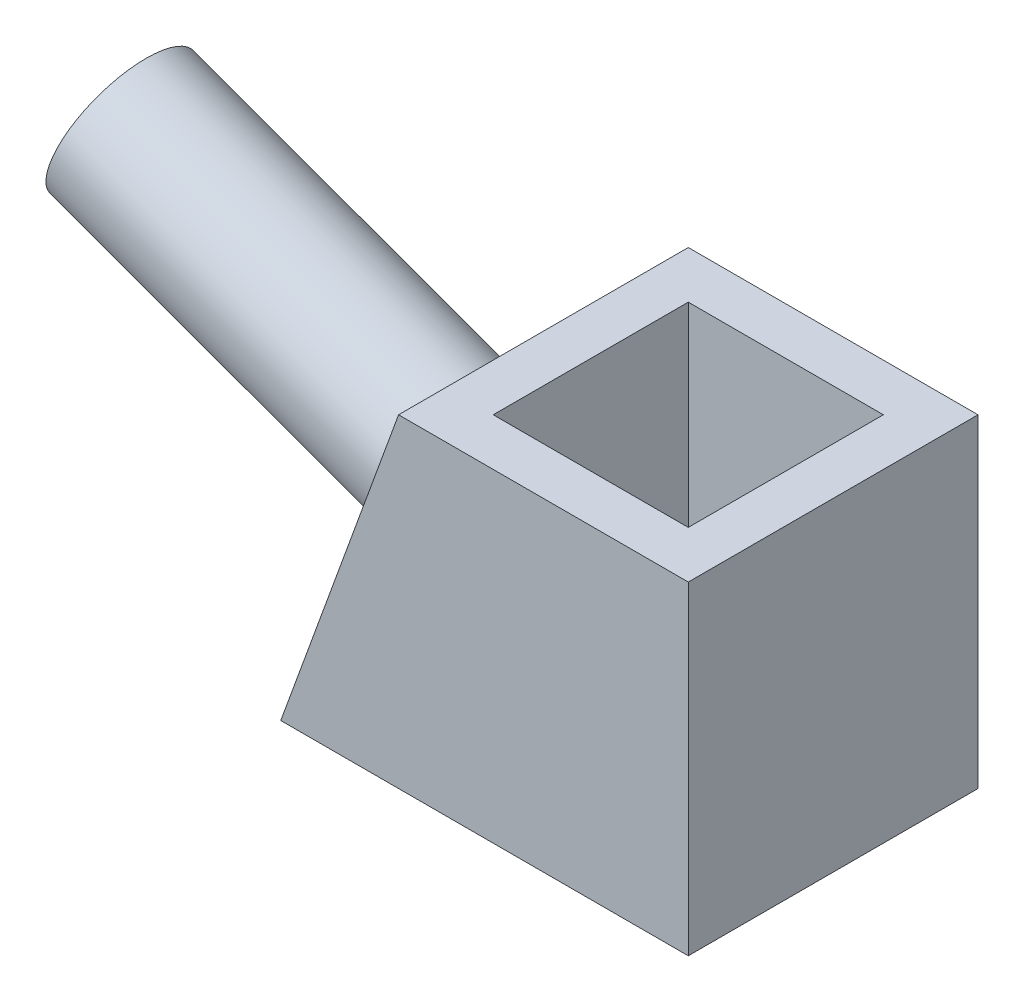
SolidWorks part; units mm, degrees
note: '?' marks a value the reader was unsure of.
ref_plane "Front Plane" through (0, 0, 0) normal (0, 0, 1) x (1, 0, 0)
ref_plane "Top Plane" through (0, 0, 0) normal (0, 1, 0) x (1, 0, 0)
ref_plane "Right Plane" through (0, 0, 0) normal (1, 0, 0) x (0, 0, -1)
sketch "Sketch1" plane through (0, 0, 0) normal (0, 1, 0) x (1, 0, 0)
  line L1 (0, 0) -> (53.594, 0)
  line L2 (0, 0) -> (0, 38.1)
  line L3 (0, 38.1) -> (53.594, 38.1)
  line L4 (53.594, 0) -> (53.594, 38.1)
  dimension "D1" = 53.594
  dimension "D2" = 38.1
extrude "Boss-Extrude1" add sketch "Sketch1" along normal blind 42.5694
sketch "Sketch4" plane through (0, 0, 0) normal (0, 0, 1) x (1, 0, 0)
  line L0 (53.594, 42.5694) -> (15.494, 42.5694)
  line L1 (0, 42.5694) -> (53.594, 42.5694) construction
  line L2 (15.494, 42.5694) -> (-0.4078, -1.1203)
  line L3 (0, 42.5694) -> (0, 0)
  line L4 (0, 42.5694) -> (0, 0) construction
  line L5 (15.494, 42.5694) -> (0, 42.5694)
  line M5 (53.594, 42.5694) -> (0, 42.5694)
  line M6 (0, 42.5694) -> (0, 0)
  dimension "D1" = 38.1
  dimension "D2" = 110
extrude "Cut-Extrude1" cut sketch "Sketch4" against normal through all contours L2 M5 M6
sketch "Sketch5" plane through (0, 42.5694, 0) normal (0, 1, 0) x (1, 0, 0)
  line L7 (15.494, 0) -> (53.594, 0) construction
  line L8 (53.594, 0) -> (53.594, 38.1) construction
  line L10 (47.371, 31.877) -> (21.717, 31.877)
  line L11 (47.371, 31.877) -> (47.371, 6.223)
  line L12 (47.371, 6.223) -> (21.717, 6.223)
  line L13 (21.717, 31.877) -> (21.717, 6.223)
  line L14 (47.371, 31.877) -> (21.717, 6.223) construction
  line L15 (47.371, 6.223) -> (21.717, 31.877) construction
  point P0 (34.544, 19.05)
  point P5 (34.544, 19.05)
  dimension "D1" = 19.05
  dimension "D2" = 19.05
  dimension "D3" = 25.654
extrude "Cut-Extrude2" cut sketch "Sketch5" against normal through all
sketch "Sketch6" plane through (0, 0, 0) normal (-0.9397, 0.342, 0) x (0, 0, 1)
  line L2 (0, 45.3014) -> (0, 0) construction
  line L3 (-38.1, 45.3014) -> (0, 45.3014) construction
  circle A0 centre (-19.05, 22.6507) radius 9.4107
  point P3 (0, 0)
  point P4 (0, 0)
  point P7 (0, 22.6507)
  point P12 (-19.05, 45.3014)
  dimension "D2" = 18.8214
extrude "Boss-Extrude2" add sketch "Sketch6" along normal blind 50.8 contours A0
ref_axis "Axis1" through (-34.4053, 36.6269, -19.05) along (0.9397, -0.342, 0)?
equation "\"D2@Sketch6\"=0.751 - 0.01"
